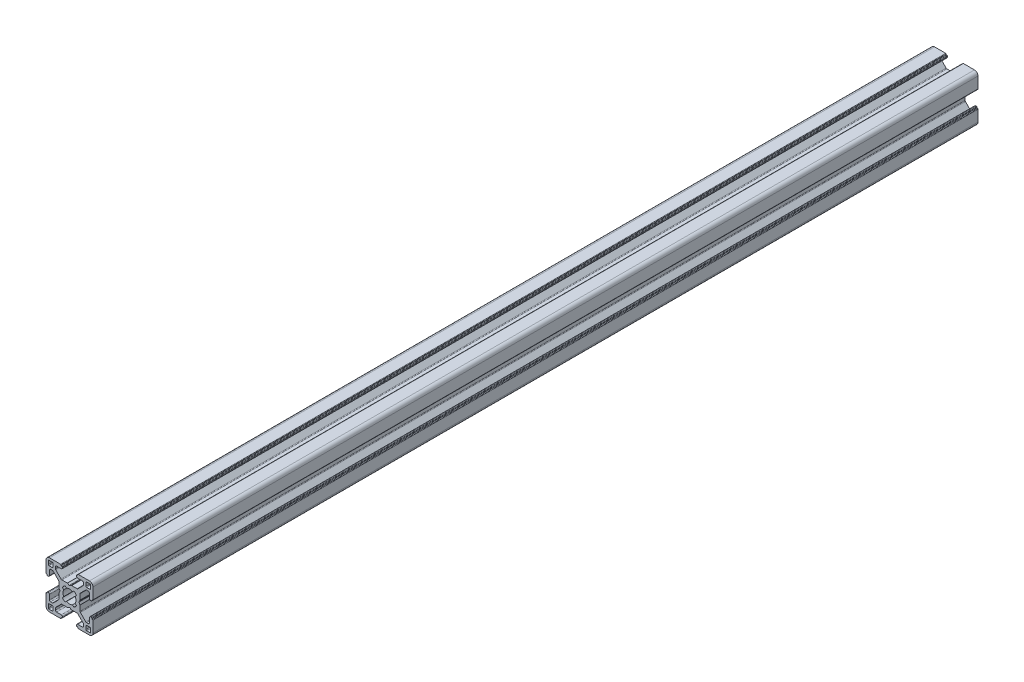
SolidWorks part; units mm, degrees
material "6063-O, Barra estrusa (SS)"
ref_plane "Piano frontale" through (0, 0, 0) normal (0, 0, 1) x (1, 0, 0)
ref_plane "Piano superiore" through (0, 0, 0) normal (0, 1, 0) x (1, 0, 0)
ref_plane "Piano destro" through (0, 0, 0) normal (1, 0, 0) x (0, 0, -1)
ref_plane "Piano1" through (0, 0, 100) normal (0, 0, 1) x (1, 0, 0)
sketch "Schizzo1" plane through (0, 0, 100) normal (0, 0, 1) x (1, 0, 0)
  line L0 (-1.9139, 2.9896) -> (-1.2582, 2.4453)
  line L1 (1.2582, 2.4453) -> (1.9139, 2.9896)
  line L2 (2.9922, 1.9099) -> (2.4453, 1.2582)
  line L3 (2.4453, -1.2582) -> (2.9922, -1.9099)
  line L4 (1.9139, -2.9896) -> (1.2582, -2.4453)
  line L5 (-1.2582, -2.4453) -> (-1.9139, -2.9896)
  line L6 (-2.9922, -1.9099) -> (-2.4453, -1.2582)
  line L7 (-2.4453, 1.2582) -> (-2.9922, 1.9099)
  line L8 (-9.3, 3) -> (-9, 3)
  line L9 (-8.5, 3.5) -> (-8.5, 5.5)
  line L10 (-8, 6) -> (-7.2678, 6)
  line L11 (-6.9142, 5.8536) -> (-4.6464, 3.5858)
  line L12 (-4.5, 3.2322) -> (-4.5, 0.9536)
  line L13 (-4.4732, 0.8536) -> (-4.0381, 0.1)
  line L14 (-4.0381, -0.1) -> (-4.4732, -0.8536)
  line L15 (-4.5, -0.9536) -> (-4.5, -3.2322)
  line L16 (-4.6464, -3.5858) -> (-6.9142, -5.8536)
  line L17 (-7.2678, -6) -> (-8, -6)
  line L18 (-8.5, -5.5) -> (-8.5, -3.5)
  line L19 (-9, -3) -> (-9.3, -3)
  line L20 (-9.5, -3.2) -> (-9.5, -3.35)
  line L21 (-9.7, -3.55) -> (-9.8, -3.55)
  line L22 (-10, -3.75) -> (-10, -8.5)
  line L23 (-8.5, -10) -> (-3.75, -10)
  line L24 (-3.55, -9.8) -> (-3.55, -9.7)
  line L25 (-3.35, -9.5) -> (-3.2, -9.5)
  line L26 (-3, -9.3) -> (-3, -9)
  line L27 (-3.5, -8.5) -> (-5.5, -8.5)
  line L28 (-6, -8) -> (-6, -7.2678)
  line L29 (-5.8536, -6.9142) -> (-3.5858, -4.6464)
  line L30 (-3.2322, -4.5) -> (-0.9536, -4.5)
  line L31 (-0.8536, -4.4732) -> (-0.1, -4.0381)
  line L32 (0.1, -4.0381) -> (0.8536, -4.4732)
  line L33 (0.9536, -4.5) -> (3.2322, -4.5)
  line L34 (3.5858, -4.6464) -> (5.8536, -6.9142)
  line L35 (6, -7.2678) -> (6, -8)
  line L36 (5.5, -8.5) -> (3.5, -8.5)
  line L37 (3, -9) -> (3, -9.3)
  line L38 (3.2, -9.5) -> (3.35, -9.5)
  line L39 (3.55, -9.7) -> (3.55, -9.8)
  line L40 (3.75, -10) -> (8.5, -10)
  line L41 (10, -8.5) -> (10, -3.75)
  line L42 (9.8, -3.55) -> (9.7, -3.55)
  line L43 (9.5, -3.35) -> (9.5, -3.2)
  line L44 (9.3, -3) -> (9, -3)
  line L45 (8.5, -3.5) -> (8.5, -5.5)
  line L46 (8, -6) -> (7.2678, -6)
  line L47 (6.9142, -5.8536) -> (4.6464, -3.5858)
  line L48 (4.5, -3.2322) -> (4.5, -0.9536)
  line L49 (4.4732, -0.8536) -> (4.0381, -0.1)
  line L50 (4.0381, 0.1) -> (4.4732, 0.8536)
  line L51 (4.5, 0.9536) -> (4.5, 3.2322)
  line L52 (4.6464, 3.5858) -> (6.9142, 5.8536)
  line L53 (7.2678, 6) -> (8, 6)
  line L54 (8.5, 5.5) -> (8.5, 3.5)
  line L55 (9, 3) -> (9.3, 3)
  line L56 (9.5, 3.2) -> (9.5, 3.35)
  line L57 (9.7, 3.55) -> (9.8, 3.55)
  line L58 (10, 3.75) -> (10, 8.5)
  line L59 (8.5, 10) -> (3.75, 10)
  line L60 (3.55, 9.8) -> (3.55, 9.7)
  line L61 (3.35, 9.5) -> (3.2, 9.5)
  line L62 (3, 9.3) -> (3, 9)
  line L63 (3.5, 8.5) -> (5.5, 8.5)
  line L64 (6, 8) -> (6, 7.2678)
  line L65 (5.8536, 6.9142) -> (3.5858, 4.6464)
  line L66 (3.2322, 4.5) -> (0.9536, 4.5)
  line L67 (0.8536, 4.4732) -> (0.1, 4.0381)
  line L68 (-0.1, 4.0381) -> (-0.8536, 4.4732)
  line L69 (-0.9536, 4.5) -> (-3.2322, 4.5)
  line L70 (-3.5858, 4.6464) -> (-5.8536, 6.9142)
  line L71 (-6, 7.2678) -> (-6, 8)
  line L72 (-5.5, 8.5) -> (-3.5, 8.5)
  line L73 (-3, 9) -> (-3, 9.3)
  line L74 (-3.2, 9.5) -> (-3.35, 9.5)
  line L75 (-3.55, 9.7) -> (-3.55, 9.8)
  line L76 (-3.75, 10) -> (-8.5, 10)
  line L77 (-10, 8.5) -> (-10, 3.75)
  line L78 (-9.8, 3.55) -> (-9.7, 3.55)
  line L79 (-9.5, 3.35) -> (-9.5, 3.2)
  line L80 (8.7, 7) -> (7.3, 7)
  line L81 (-7.3, 7) -> (-8.7, 7)
  line L82 (-7, 7.3) -> (-7, 8.7)
  line L83 (-7.3, 9) -> (-8.7, 9)
  line L84 (-9, 7.3) -> (-9, 8.7)
  line L85 (9, 7.3) -> (9, 8.7)
  line L86 (8.7, 9) -> (7.3, 9)
  line L87 (7, 7.3) -> (7, 8.7)
  line L88 (8.7, -9) -> (7.3, -9)
  line L89 (9, -8.7) -> (9, -7.3)
  line L90 (8.7, -7) -> (7.3, -7)
  line L91 (7, -8.7) -> (7, -7.3)
  line L92 (-7.3, -9) -> (-8.7, -9)
  line L93 (-7, -8.7) -> (-7, -7.3)
  line L94 (-7.3, -7) -> (-8.7, -7)
  line L95 (-9, -8.7) -> (-9, -7.3)
  arc A0 (-1.2582, 2.4453) -> (1.2582, 2.4453) centre (0, 0) cw
  arc A1 (1.9139, 2.9896) -> (2.9922, 1.9099) centre (0, 0) cw
  arc A2 (2.4453, 1.2582) -> (2.4453, -1.2582) centre (0, 0) cw
  arc A3 (2.9922, -1.9099) -> (1.9139, -2.9896) centre (0, 0) cw
  arc A4 (1.2582, -2.4453) -> (-1.2582, -2.4453) centre (0, 0) cw
  arc A5 (-1.9139, -2.9896) -> (-2.9922, -1.9099) centre (0, 0) cw
  arc A6 (-2.4453, -1.2582) -> (-2.4453, 1.2582) centre (0, 0) cw
  arc A7 (-2.9922, 1.9099) -> (-1.9139, 2.9896) centre (0, 0) cw
  arc A8 (-9.5, 3.2) -> (-9.3, 3) centre (-9.3, 3.2) ccw
  arc A9 (-9, 3) -> (-8.5, 3.5) centre (-9, 3.5) ccw
  arc A10 (-8.5, 5.5) -> (-8, 6) centre (-8, 5.5) cw
  arc A11 (-7.2678, 6) -> (-6.9142, 5.8536) centre (-7.2678, 5.5) cw
  arc A12 (-4.6464, 3.5858) -> (-4.5, 3.2322) centre (-5, 3.2322) cw
  arc A13 (-4.5, 0.9536) -> (-4.4732, 0.8536) centre (-4.3, 0.9536) ccw
  arc A14 (-4.0381, 0.1) -> (-4.0381, -0.1) centre (-4.2113, 0) cw
  arc A15 (-4.4732, -0.8536) -> (-4.5, -0.9536) centre (-4.3, -0.9536) ccw
  arc A16 (-4.5, -3.2322) -> (-4.6464, -3.5858) centre (-5, -3.2322) cw
  arc A17 (-6.9142, -5.8536) -> (-7.2678, -6) centre (-7.2678, -5.5) cw
  arc A18 (-8, -6) -> (-8.5, -5.5) centre (-8, -5.5) cw
  arc A19 (-8.5, -3.5) -> (-9, -3) centre (-9, -3.5) ccw
  arc A20 (-9.3, -3) -> (-9.5, -3.2) centre (-9.3, -3.2) ccw
  arc A21 (-9.5, -3.35) -> (-9.7, -3.55) centre (-9.7, -3.35) cw
  arc A22 (-9.8, -3.55) -> (-10, -3.75) centre (-9.8, -3.75) ccw
  arc A23 (-10, -8.5) -> (-8.5, -10) centre (-8.5, -8.5) ccw
  arc A24 (-3.75, -10) -> (-3.55, -9.8) centre (-3.75, -9.8) ccw
  arc A25 (-3.55, -9.7) -> (-3.35, -9.5) centre (-3.35, -9.7) cw
  arc A26 (-3.2, -9.5) -> (-3, -9.3) centre (-3.2, -9.3) ccw
  arc A27 (-3, -9) -> (-3.5, -8.5) centre (-3.5, -9) ccw
  arc A28 (-5.5, -8.5) -> (-6, -8) centre (-5.5, -8) cw
  arc A29 (-6, -7.2678) -> (-5.8536, -6.9142) centre (-5.5, -7.2678) cw
  arc A30 (-3.5858, -4.6464) -> (-3.2322, -4.5) centre (-3.2322, -5) cw
  arc A31 (-0.9536, -4.5) -> (-0.8536, -4.4732) centre (-0.9536, -4.3) ccw
  arc A32 (-0.1, -4.0381) -> (0.1, -4.0381) centre (0, -4.2113) cw
  arc A33 (0.8536, -4.4732) -> (0.9536, -4.5) centre (0.9536, -4.3) ccw
  arc A34 (3.2322, -4.5) -> (3.5858, -4.6464) centre (3.2322, -5) cw
  arc A35 (5.8536, -6.9142) -> (6, -7.2678) centre (5.5, -7.2678) cw
  arc A36 (6, -8) -> (5.5, -8.5) centre (5.5, -8) cw
  arc A37 (3.5, -8.5) -> (3, -9) centre (3.5, -9) ccw
  arc A38 (3, -9.3) -> (3.2, -9.5) centre (3.2, -9.3) ccw
  arc A39 (3.35, -9.5) -> (3.55, -9.7) centre (3.35, -9.7) cw
  arc A40 (3.55, -9.8) -> (3.75, -10) centre (3.75, -9.8) ccw
  arc A41 (8.5, -10) -> (10, -8.5) centre (8.5, -8.5) ccw
  arc A42 (10, -3.75) -> (9.8, -3.55) centre (9.8, -3.75) ccw
  arc A43 (9.7, -3.55) -> (9.5, -3.35) centre (9.7, -3.35) cw
  arc A44 (9.5, -3.2) -> (9.3, -3) centre (9.3, -3.2) ccw
  arc A45 (9, -3) -> (8.5, -3.5) centre (9, -3.5) ccw
  arc A46 (8.5, -5.5) -> (8, -6) centre (8, -5.5) cw
  arc A47 (7.2678, -6) -> (6.9142, -5.8536) centre (7.2678, -5.5) cw
  arc A48 (4.6464, -3.5858) -> (4.5, -3.2322) centre (5, -3.2322) cw
  arc A49 (4.5, -0.9536) -> (4.4732, -0.8536) centre (4.3, -0.9536) ccw
  arc A50 (4.0381, -0.1) -> (4.0381, 0.1) centre (4.2113, 0) cw
  arc A51 (4.4732, 0.8536) -> (4.5, 0.9536) centre (4.3, 0.9536) ccw
  arc A52 (4.5, 3.2322) -> (4.6464, 3.5858) centre (5, 3.2322) cw
  arc A53 (6.9142, 5.8536) -> (7.2678, 6) centre (7.2678, 5.5) cw
  arc A54 (8, 6) -> (8.5, 5.5) centre (8, 5.5) cw
  arc A55 (8.5, 3.5) -> (9, 3) centre (9, 3.5) ccw
  arc A56 (9.3, 3) -> (9.5, 3.2) centre (9.3, 3.2) ccw
  arc A57 (9.5, 3.35) -> (9.7, 3.55) centre (9.7, 3.35) cw
  arc A58 (9.8, 3.55) -> (10, 3.75) centre (9.8, 3.75) ccw
  arc A59 (10, 8.5) -> (8.5, 10) centre (8.5, 8.5) ccw
  arc A60 (3.75, 10) -> (3.55, 9.8) centre (3.75, 9.8) ccw
  arc A61 (3.55, 9.7) -> (3.35, 9.5) centre (3.35, 9.7) cw
  arc A62 (3.2, 9.5) -> (3, 9.3) centre (3.2, 9.3) ccw
  arc A63 (3, 9) -> (3.5, 8.5) centre (3.5, 9) ccw
  arc A64 (5.5, 8.5) -> (6, 8) centre (5.5, 8) cw
  arc A65 (6, 7.2678) -> (5.8536, 6.9142) centre (5.5, 7.2678) cw
  arc A66 (3.5858, 4.6464) -> (3.2322, 4.5) centre (3.2322, 5) cw
  arc A67 (0.9536, 4.5) -> (0.8536, 4.4732) centre (0.9536, 4.3) ccw
  arc A68 (0.1, 4.0381) -> (-0.1, 4.0381) centre (0, 4.2113) cw
  arc A69 (-0.8536, 4.4732) -> (-0.9536, 4.5) centre (-0.9536, 4.3) ccw
  arc A70 (-3.2322, 4.5) -> (-3.5858, 4.6464) centre (-3.2322, 5) cw
  arc A71 (-5.8536, 6.9142) -> (-6, 7.2678) centre (-5.5, 7.2678) cw
  arc A72 (-6, 8) -> (-5.5, 8.5) centre (-5.5, 8) cw
  arc A73 (-3.5, 8.5) -> (-3, 9) centre (-3.5, 9) ccw
  arc A74 (-3, 9.3) -> (-3.2, 9.5) centre (-3.2, 9.3) ccw
  arc A75 (-3.35, 9.5) -> (-3.55, 9.7) centre (-3.35, 9.7) cw
  arc A76 (-3.55, 9.8) -> (-3.75, 10) centre (-3.75, 9.8) ccw
  arc A77 (-8.5, 10) -> (-10, 8.5) centre (-8.5, 8.5) ccw
  arc A78 (-10, 3.75) -> (-9.8, 3.55) centre (-9.8, 3.75) ccw
  arc A79 (-9.7, 3.55) -> (-9.5, 3.35) centre (-9.7, 3.35) cw
  arc A80 (-8.7, 7) -> (-9, 7.3) centre (-8.7, 7.3) cw
  arc A81 (-7, 8.7) -> (-7.3, 9) centre (-7.3, 8.7) ccw
  arc A82 (-7.3, 7) -> (-7, 7.3) centre (-7.3, 7.3) ccw
  arc A83 (-8.7, 9) -> (-9, 8.7) centre (-8.7, 8.7) ccw
  arc A84 (7.3, 7) -> (7, 7.3) centre (7.3, 7.3) cw
  arc A85 (9, 8.7) -> (8.7, 9) centre (8.7, 8.7) ccw
  arc A86 (8.7, 7) -> (9, 7.3) centre (8.7, 7.3) ccw
  arc A87 (7.3, 9) -> (7, 8.7) centre (7.3, 8.7) ccw
  arc A88 (7.3, -9) -> (7, -8.7) centre (7.3, -8.7) cw
  arc A89 (9, -7.3) -> (8.7, -7) centre (8.7, -7.3) ccw
  arc A90 (8.7, -9) -> (9, -8.7) centre (8.7, -8.7) ccw
  arc A91 (7.3, -7) -> (7, -7.3) centre (7.3, -7.3) ccw
  arc A92 (-8.7, -9) -> (-9, -8.7) centre (-8.7, -8.7) cw
  arc A93 (-7, -7.3) -> (-7.3, -7) centre (-7.3, -7.3) ccw
  arc A94 (-7.3, -9) -> (-7, -8.7) centre (-7.3, -8.7) ccw
  arc A95 (-8.7, -7) -> (-9, -7.3) centre (-8.7, -7.3) ccw
  dimension "D1" = 0.3
  dimension "D2" = 1
  dimension "D3" = 1
  dimension "D4" = 1
  dimension "D7" = 1
  dimension "D8" = 1
  dimension "D9" = 1
  dimension "D10" = 1
  dimension "D5" = 2
  dimension "D6" = 2
extrude "Estrusione-Estrusione1" add sketch "Schizzo1" against normal blind 377
